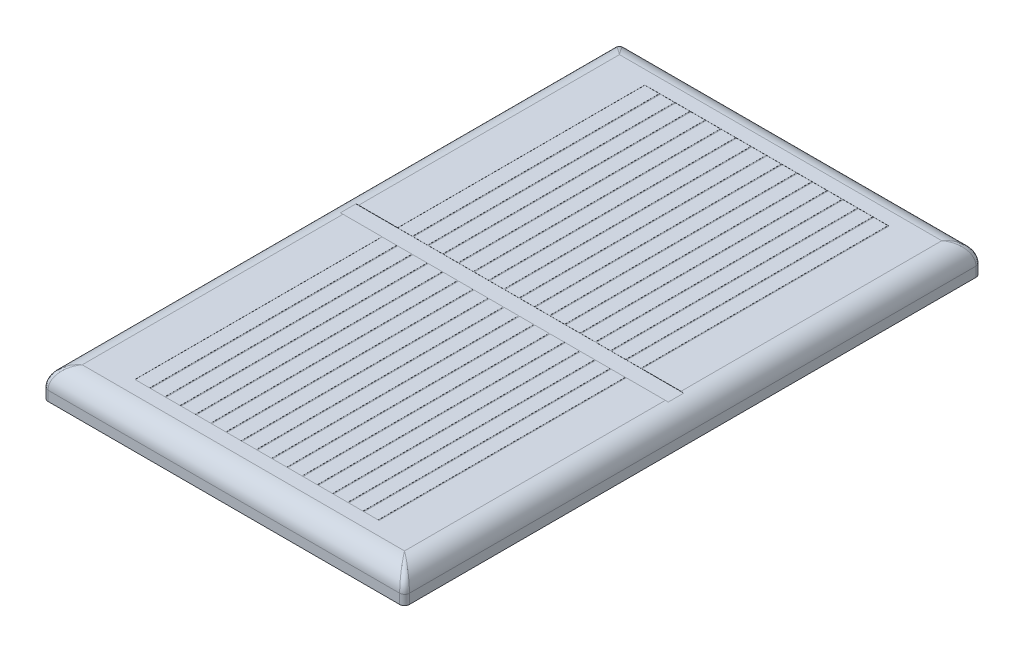
SolidWorks part; units mm, degrees
ref_plane "Front Plane" through (0, 0, 0) normal (0, 0, 1) x (1, 0, 0)
ref_plane "Top Plane" through (0, 0, 0) normal (0, 1, 0) x (1, 0, 0)
ref_plane "Right Plane" through (0, 0, 0) normal (1, 0, 0) x (0, 0, -1)
sketch "BaseS" plane through (0, 0, 0) normal (0, 1, 0) x (1, 0, 0)
  line L1 (-18.5, 29.5) -> (18.5, 29.5)
  line L2 (-18.5, 29.5) -> (-18.5, -29.5)
  line L3 (-18.5, -29.5) -> (18.5, -29.5)
  line L4 (18.5, 29.5) -> (18.5, -29.5)
  line L5 (-18.5, 29.5) -> (18.5, -29.5) construction
  line L6 (-18.5, -29.5) -> (18.5, 29.5) construction
  point P0 (0, 0)
  dimension "Width" = 59
  dimension "Length" = 37
extrude "Base" add sketch "BaseS" along normal mid plane 3
sketch "MainSolderPointS" plane through (0, -1.5, 0) normal (0, -1, 0) x (-1, 0, 0)
  line L4 (-18.5, 29.5) -> (18.5, 29.5) construction
  circle A0 centre (-5, 14.5) radius 1.5
  point P4 (0, 0)
  point P5 (0, 0)
  dimension "Dia" = 3
  dimension "XDim" = 5
  dimension "YDim" = 15
extrude "MainSolderPoint" add sketch "MainSolderPointS" along normal blind 0.01
sketch "SolderPointS" plane through (0, -1.5, 0) normal (0, -1, 0) x (-1, 0, 0)
  line L0 (-18.5, 0) -> (-15.5, 0) construction
  line L5 (-18.5, -29.5) -> (-18.5, 29.5) construction
  circle A0 centre (-15.5, 0) radius 1.5
  dimension "Dia" = 3
  dimension "XDim" = 3
extrude "SolderPoint" add sketch "SolderPointS" along normal blind 0.01
sketch "SolderLegS" plane through (0, -1.5, 0) normal (0, -1, 0) x (-1, 0, 0)
  line L0 (-14, 0) -> (-15.5, 0) construction
  line L1 (-5, -1.5) -> (-15.5, -1.5)
  line L2 (-6.7, 1.5) -> (-15.5, 1.5)
  line L3 (-5, 0) -> (-5, 14.5) construction
  line L4 (-6.5, 1.7) -> (-6.5, 14.5)
  line L5 (-3.5, 0) -> (-3.5, 14.5)
  line L6 (-3.5, 14.5) -> (-6.5, 14.5) construction
  line L7 (-15.5, 1.5) -> (-15.5, -1.5) construction
  arc A0 (-5, -1.5) -> (-3.5, 0) centre (-5, 0) ccw
  arc A2 (-5, -1.5) -> (-3.5, 0) centre (-5, 0) ccw
  circle A4 centre (-5, 14.5) radius 1.5 construction
  arc A5 (-6.5, 14.5) -> (-3.5, 14.5) centre (-5, 14.5) ccw
  circle A6 centre (-15.5, 0) radius 1.5 construction
  circle A7 centre (-15.5, 0) radius 1.5 construction
  arc A8 (-15.5, -1.5) -> (-15.5, 1.5) centre (-15.5, 0) ccw
  circle A9 centre (-5, 14.5) radius 1.5 construction
  arc A10 (-6.7, 1.5) -> (-6.5, 1.7) centre (-6.7, 1.7) ccw
  point P1 (-15.6624, -1.4912)
  point P3 (0, 0)
  point P8 (-15.3716, 0)
  point P12 (-5, -1.5)
  point P13 (0, 0)
  point P24 (-5, -1.5)
  point P25 (-3.5, 0)
  point P26 (0, 0)
  circle M7 centre (-15.5, 0) radius 1.5
  circle M8 centre (-5, 14.5) radius 1.5
  dimension "InnerTurnRadius" = 0.2
extrude "SolderLeg" add sketch "SolderLegS" along normal blind 0.005 contours A10 L2 L1 A0 L5 L4 M7 M8
mirror "SPPHM" about plane through (0, 0, 0) normal (1, 0, 0) of "SolderLeg", "SolderPoint", "MainSolderPoint"
sketch "PolaritySignsS" plane through (0, -1.5, 0) normal (0, -1, 0) x (-1, 0, 0)
  line L0 (-5, 14.5) -> (-13, 14.5) construction
  line L1 (0, 0) -> (0, 4.5) construction
  line L2 (15.25, 14.5) -> (10.75, 14.5) construction
  line L3 (-10.75, 14.25) -> (-15.25, 14.25)
  line L4 (-10.75, 14.25) -> (-10.75, 14.75)
  line L5 (-10.75, 14.75) -> (-15.25, 14.75)
  line L6 (-15.25, 14.25) -> (-15.25, 14.75)
  line L7 (-10.75, 14.25) -> (-15.25, 14.75) construction
  line L8 (-10.75, 14.75) -> (-15.25, 14.25) construction
  line L9 (15.25, 14.25) -> (13.25, 14.25)
  line L10 (15.25, 14.25) -> (15.25, 14.75)
  line L11 (15.25, 14.75) -> (13.25, 14.75)
  line L12 (10.75, 14.25) -> (10.75, 14.75)
  line L13 (15.25, 14.25) -> (10.75, 14.75) construction
  line L14 (15.25, 14.75) -> (10.75, 14.25) construction
  line L15 (13.25, 12.25) -> (12.75, 12.25)
  line L16 (13.25, 12.25) -> (13.25, 14.25)
  line L17 (13.25, 16.75) -> (12.75, 16.75)
  line L18 (12.75, 12.25) -> (12.75, 14.25)
  line L19 (13.25, 12.25) -> (12.75, 16.75) construction
  line L20 (13.25, 16.75) -> (12.75, 12.25) construction
  line L21 (12.75, 14.75) -> (10.75, 14.75)
  line L22 (12.75, 14.75) -> (12.75, 16.75)
  line L24 (13.25, 14.75) -> (13.25, 16.75)
  line L25 (12.75, 14.25) -> (10.75, 14.25)
  circle A0 centre (-13, 14.5) radius 2.25 construction
  circle A2 centre (13, 14.5) radius 2.25 construction
  point P4 (-5, 14.42)
  point P5 (-7.4, 18.4469)
  point P6 (-12.6633, 14.5)
  point P8 (0, 0)
  dimension "Dia" = 4.5
  dimension "Height" = 0.5
  dimension "XDim" = 8
extrude "PolaritySigns" add sketch "PolaritySignsS" along normal blind 0.005
sketch "LightAbsorptionSectionS" plane through (0, 1.5, 0) normal (0, 1, 0) x (1, 0, 0)
  line L0 (18.5, 29.5) -> (-18.5, 29.5) construction
  line L1 (12.5, 26.1) -> (-12.5, 26.1)
  line L2 (12.5, 26.1) -> (12.5, -26.1)
  line L3 (12.5, -26.1) -> (-12.5, -26.1)
  line L4 (-12.5, 26.1) -> (-12.5, -26.1)
  line L5 (-12.5, 0) -> (-18.5, 0) construction
  line L9 (0, 26.1) -> (0, 29.5) construction
  line L10 (-18.5, 29.5) -> (-18.5, -29.5) construction
  dimension "XDist" = 3.4
  dimension "RefWidth" = 52.2
  dimension "YDist" = 6
  dimension "RefLength" = 25
extrude "LightAbsorptionSection" cut sketch "LightAbsorptionSectionS" against normal blind 0.01
sketch "LASSlotS" plane through (0, 1.49, 0) normal (0, 1, 0) x (1, 0, 0)
  line L0 (12.5, -26.1) -> (-12.5, -26.1) construction
  line L1 (12.5, 26.1) -> (12.4, 26.1)
  line L2 (12.5, 26.1) -> (12.5, -26.1)
  line L3 (12.5, -26.1) -> (12.4, -26.1)
  line L4 (12.4, 26.1) -> (12.4, -26.1)
  dimension "Thickness" = 0.1
extrude "LASSlot" cut sketch "LASSlotS" against normal blind 0.01
pattern_linear "LASSlot LP" count 16 spacing 1.56 along (-1, 0, 0) of "LASSlot"
sketch "CircuitConnectionS" plane through (0, 1.5, 0) normal (0, 1, 0) x (1, 0, 0)
  line L0 (-18.5, 29.5) -> (-18.5, -29.5) construction
  line L1 (-18, 0.8) -> (18, 0.8)
  line L2 (-18, 0.8) -> (-18, -0.8)
  line L3 (-18, -0.8) -> (18, -0.8)
  line L4 (18, 0.8) -> (18, -0.8)
  line L5 (-18, 0.8) -> (18, -0.8) construction
  line L6 (-18, -0.8) -> (18, 0.8) construction
  point P0 (0, 0)
  dimension "Width" = 1.6
  dimension "LengthControl" = 0.5
extrude "CircuitConnection" cut sketch "CircuitConnectionS" against normal up to surface (0.02 mm away) up to face at (12.45, 1.48, 0)
fillet "BaseF" radius 2 4 edges at (0, 1.5, 29.5) (-18.5, 1.5, 0) (0, 1.5, -29.5) (18.5, 1.5, 0)
fillet "BaseCornerF" radius 0.5 8 edges at (-17.9142, 0.9142, -28.9142) (17.9142, 0.9142, -28.9142) (17.9142, 0.9142, 28.9142) (-17.9142, 0.9142, 28.9142) (-18.5, -1, -29.5) (18.5, -1, -29.5) (18.5, -1, 29.5) (-18.5, -1, 29.5)
equation "\"NumInstances@LASSlot LP\"=\"RefLength@LightAbsorptionSectionS\"/\"Dist@LASSlot LP\""
